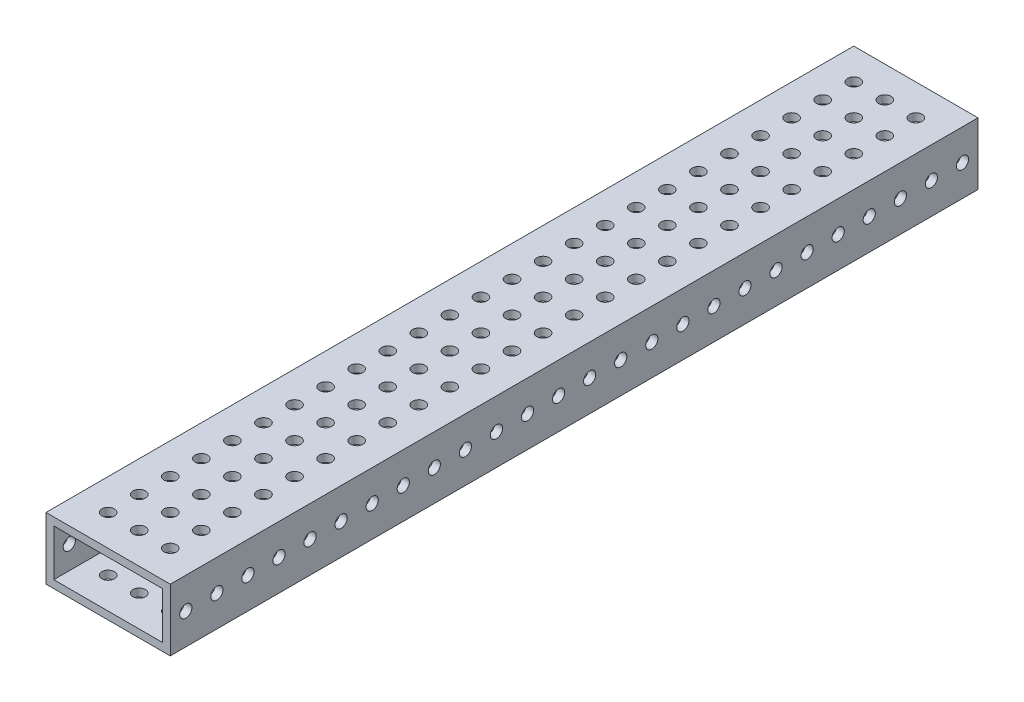
SolidWorks part; units mm, degrees
material "6061-T6 (SS)"
ref_plane "Front Plane" through (0, 0, 0) normal (0, 0, 1) x (1, 0, 0)
ref_plane "Top Plane" through (0, 0, 0) normal (0, 1, 0) x (1, 0, 0)
ref_plane "Right Plane" through (0, 0, 0) normal (1, 0, 0) x (0, 0, -1)
sketch "Sketch1" plane through (0, 0, 0) normal (0, 0, 1) x (1, 0, 0)
  line L0 (-22.225, 9.525) -> (22.225, 9.525)
  line L1 (-25.4, 12.7) -> (25.4, 12.7)
  line L2 (-25.4, 12.7) -> (-25.4, -12.7)
  line L3 (-25.4, -12.7) -> (25.4, -12.7)
  line L4 (25.4, 12.7) -> (25.4, -12.7)
  line L5 (22.225, 9.525) -> (22.225, -9.525)
  line L6 (-22.225, -9.525) -> (22.225, -9.525)
  line L7 (-22.225, 9.525) -> (-22.225, -9.525)
  line L8 (-25.4, 12.7) -> (25.4, -12.7) construction
  line L9 (25.4, 12.7) -> (-25.4, -12.7) construction
  point P5 (0, 0)
  dimension "D1" = 50.8
  dimension "D2" = 25.4
  dimension "D3" = 3.175
extrude "Boss-Extrude1" add sketch "Sketch1" along normal mid plane 330.2
sketch "Sketch2" plane through (0, 12.7, 0) normal (0, 1, 0) x (1, 0, 0)
  line L0 (25.4, -165.1) -> (-25.4, -165.1) construction
  line L1 (-25.4, -165.1) -> (-25.4, 165.1) construction
  line L2 (-12.7, -152.4) -> (0, -152.4) construction
  line L3 (0, -152.4) -> (12.7, -152.4) construction
  line L4 (25.4, 165.1) -> (-25.4, 165.1) construction
  circle A0 centre (0, -152.4) radius 2.5527
  circle A1 centre (12.7, -152.4) radius 2.5527
  circle A2 centre (-12.7, -152.4) radius 2.5527
  circle A3 centre (-12.7, -139.7) radius 2.5527
  circle A4 centre (0, -139.7) radius 2.5527
  circle A5 centre (12.7, -139.7) radius 2.5527
  circle A6 centre (-12.7, -127) radius 2.5527
  circle A7 centre (0, -127) radius 2.5527
  circle A8 centre (12.7, -127) radius 2.5527
  circle A9 centre (-12.7, -114.3) radius 2.5527
  circle A10 centre (0, -114.3) radius 2.5527
  circle A11 centre (12.7, -114.3) radius 2.5527
  circle A12 centre (-12.7, -101.6) radius 2.5527
  circle A13 centre (0, -101.6) radius 2.5527
  circle A14 centre (12.7, -101.6) radius 2.5527
  circle A15 centre (-12.7, -88.9) radius 2.5527
  circle A16 centre (0, -88.9) radius 2.5527
  circle A17 centre (12.7, -88.9) radius 2.5527
  circle A18 centre (-12.7, -76.2) radius 2.5527
  circle A19 centre (0, -76.2) radius 2.5527
  circle A20 centre (12.7, -76.2) radius 2.5527
  circle A21 centre (-12.7, -63.5) radius 2.5527
  circle A22 centre (0, -63.5) radius 2.5527
  circle A23 centre (12.7, -63.5) radius 2.5527
  circle A24 centre (-12.7, -50.8) radius 2.5527
  circle A25 centre (0, -50.8) radius 2.5527
  circle A26 centre (12.7, -50.8) radius 2.5527
  circle A27 centre (-12.7, -38.1) radius 2.5527
  circle A28 centre (0, -38.1) radius 2.5527
  circle A29 centre (12.7, -38.1) radius 2.5527
  circle A30 centre (-12.7, -25.4) radius 2.5527
  circle A31 centre (0, -25.4) radius 2.5527
  circle A32 centre (12.7, -25.4) radius 2.5527
  circle A33 centre (-12.7, -12.7) radius 2.5527
  circle A34 centre (0, -12.7) radius 2.5527
  circle A35 centre (12.7, -12.7) radius 2.5527
  circle A36 centre (-12.7, 0) radius 2.5527
  circle A37 centre (0, 0) radius 2.5527
  circle A38 centre (12.7, 0) radius 2.5527
  circle A39 centre (-12.7, 12.7) radius 2.5527
  circle A40 centre (0, 12.7) radius 2.5527
  circle A41 centre (12.7, 12.7) radius 2.5527
  circle A42 centre (-12.7, 25.4) radius 2.5527
  circle A43 centre (0, 25.4) radius 2.5527
  circle A44 centre (12.7, 25.4) radius 2.5527
  circle A45 centre (-12.7, 38.1) radius 2.5527
  circle A46 centre (0, 38.1) radius 2.5527
  circle A47 centre (12.7, 38.1) radius 2.5527
  circle A48 centre (-12.7, 50.8) radius 2.5527
  circle A49 centre (0, 50.8) radius 2.5527
  circle A50 centre (12.7, 50.8) radius 2.5527
  circle A51 centre (-12.7, 63.5) radius 2.5527
  circle A52 centre (0, 63.5) radius 2.5527
  circle A53 centre (12.7, 63.5) radius 2.5527
  circle A54 centre (-12.7, 76.2) radius 2.5527
  circle A55 centre (0, 76.2) radius 2.5527
  circle A56 centre (12.7, 76.2) radius 2.5527
  circle A57 centre (-12.7, 88.9) radius 2.5527
  circle A58 centre (0, 88.9) radius 2.5527
  circle A59 centre (12.7, 88.9) radius 2.5527
  circle A60 centre (-12.7, 101.6) radius 2.5527
  circle A61 centre (0, 101.6) radius 2.5527
  circle A62 centre (12.7, 101.6) radius 2.5527
  circle A63 centre (-12.7, 114.3) radius 2.5527
  circle A64 centre (0, 114.3) radius 2.5527
  circle A65 centre (12.7, 114.3) radius 2.5527
  circle A66 centre (-12.7, 127) radius 2.5527
  circle A67 centre (0, 127) radius 2.5527
  circle A68 centre (12.7, 127) radius 2.5527
  circle A69 centre (-12.7, 139.7) radius 2.5527
  circle A70 centre (0, 139.7) radius 2.5527
  circle A71 centre (12.7, 139.7) radius 2.5527
  circle A72 centre (-12.7, 152.4) radius 2.5527
  circle A73 centre (0, 152.4) radius 2.5527
  circle A74 centre (12.7, 152.4) radius 2.5527
  circle A75 centre (-12.7, 165.1) radius 2.5527 construction
  circle A76 centre (0, 165.1) radius 2.5527 construction
  circle A77 centre (12.7, 165.1) radius 2.5527 construction
  circle A78 centre (-12.7, 177.8) radius 2.5527
  circle A79 centre (0, 177.8) radius 2.5527
  circle A80 centre (12.7, 177.8) radius 2.5527
  circle A81 centre (-12.7, 190.5) radius 2.5527
  circle A82 centre (0, 190.5) radius 2.5527
  circle A83 centre (12.7, 190.5) radius 2.5527
  circle A84 centre (-12.7, 203.2) radius 2.5527
  circle A85 centre (0, 203.2) radius 2.5527
  circle A86 centre (12.7, 203.2) radius 2.5527
  circle A87 centre (-12.7, 215.9) radius 2.5527
  circle A88 centre (0, 215.9) radius 2.5527
  circle A89 centre (12.7, 215.9) radius 2.5527
  circle A90 centre (-12.7, 228.6) radius 2.5527
  circle A91 centre (0, 228.6) radius 2.5527
  circle A92 centre (12.7, 228.6) radius 2.5527
  circle A93 centre (-12.7, 241.3) radius 2.5527
  circle A94 centre (0, 241.3) radius 2.5527
  circle A95 centre (12.7, 241.3) radius 2.5527
  circle A96 centre (-12.7, 254) radius 2.5527
  circle A97 centre (0, 254) radius 2.5527
  circle A98 centre (12.7, 254) radius 2.5527
  circle A99 centre (-12.7, 266.7) radius 2.5527
  circle A100 centre (0, 266.7) radius 2.5527
  circle A101 centre (12.7, 266.7) radius 2.5527
  circle A108 centre (-12.7, 292.1) radius 2.5527 [skipped]
  circle A109 centre (0, 292.1) radius 2.5527 [skipped]
  circle A110 centre (12.7, 292.1) radius 2.5527 [skipped]
  circle A111 centre (-12.7, 279.4) radius 2.5527 [skipped]
  circle A112 centre (0, 279.4) radius 2.5527 [skipped]
  circle A113 centre (12.7, 279.4) radius 2.5527 [skipped]
  circle A114 centre (12.7, 279.4) radius 2.5527
  circle A115 centre (0, 279.4) radius 2.5527
  circle A116 centre (-12.7, 279.4) radius 2.5527
  circle A117 centre (12.7, 292.1) radius 2.5527
  circle A118 centre (0, 292.1) radius 2.5527
  circle A119 centre (-12.7, 292.1) radius 2.5527
  circle A120 centre (12.7, 304.8) radius 2.5527
  circle A121 centre (0, 304.8) radius 2.5527
  circle A122 centre (-12.7, 304.8) radius 2.5527
  circle A123 centre (12.7, 317.5) radius 2.5527
  circle A124 centre (0, 317.5) radius 2.5527
  circle A125 centre (-12.7, 317.5) radius 2.5527
  circle A126 centre (12.7, 330.2) radius 2.5527
  circle A127 centre (0, 330.2) radius 2.5527
  circle A128 centre (-12.7, 330.2) radius 2.5527
  circle A129 centre (12.7, 342.9) radius 2.5527
  circle A130 centre (0, 342.9) radius 2.5527
  circle A131 centre (-12.7, 342.9) radius 2.5527
  circle A132 centre (12.7, 355.6) radius 2.5527
  circle A133 centre (0, 355.6) radius 2.5527
  circle A134 centre (-12.7, 355.6) radius 2.5527
  circle A135 centre (12.7, 368.3) radius 2.5527
  circle A136 centre (0, 368.3) radius 2.5527
  circle A137 centre (-12.7, 368.3) radius 2.5527
  circle A138 centre (12.7, 381) radius 2.5527
  circle A139 centre (0, 381) radius 2.5527
  circle A140 centre (-12.7, 381) radius 2.5527
  circle A141 centre (12.7, 393.7) radius 2.5527
  circle A142 centre (0, 393.7) radius 2.5527
  circle A143 centre (-12.7, 393.7) radius 2.5527
  circle A144 centre (12.7, 406.4) radius 2.5527
  circle A145 centre (0, 406.4) radius 2.5527
  circle A146 centre (-12.7, 406.4) radius 2.5527
  circle A147 centre (12.7, 419.1) radius 2.5527
  circle A148 centre (0, 419.1) radius 2.5527
  circle A149 centre (-12.7, 419.1) radius 2.5527
  circle A150 centre (12.7, 431.8) radius 2.5527
  circle A151 centre (0, 431.8) radius 2.5527
  circle A152 centre (-12.7, 431.8) radius 2.5527
  point P210 (0, 0)
  point P211 (0, 0)
  dimension "D2" = 5.1054
  dimension "D4" = 12.7
  dimension "D1" = 12.7
  dimension "D3" = 25.4
  dimension "D6" = 12.7
  dimension "D7" = 101.6
  dimension "D5" = 36
  dimension "D8" = 14
extrude "Cut-Extrude1" cut sketch "Sketch2" against normal through all
sketch "Sketch4" plane through (25.4, 0, 0) normal (1, 0, 0) x (0, 0, -1)
  line L1 (-165.1, -12.7) -> (-165.1, 12.7) construction
  line L2 (-165.1, -12.7) -> (165.1, -12.7) construction
  circle A2 centre (-158.75, 0) radius 2.4892
  circle A3 centre (-146.05, 0) radius 2.4892
  circle A16 centre (-133.35, 0) radius 2.4892
  circle A17 centre (-120.65, 0) radius 2.4892
  circle A18 centre (-107.95, 0) radius 2.4892
  circle A19 centre (273.05, 0) radius 2.4892
  circle A20 centre (285.75, 0) radius 2.4892
  circle A21 centre (298.45, 0) radius 2.4892
  circle A22 centre (311.15, 0) radius 2.4892
  circle A23 centre (323.85, 0) radius 2.4892
  circle A24 centre (336.55, 0) radius 2.4892
  circle A25 centre (349.25, 0) radius 2.4892
  circle A26 centre (361.95, 0) radius 2.4892
  circle A27 centre (374.65, 0) radius 2.4892
  circle A28 centre (387.35, 0) radius 2.4892
  circle A29 centre (400.05, 0) radius 2.4892
  circle A30 centre (412.75, 0) radius 2.4892
  circle A31 centre (425.45, 0) radius 2.4892
  circle A32 centre (438.15, 0) radius 2.4892
  circle A35 centre (-95.25, 0) radius 2.4892
  circle A36 centre (-82.55, 0) radius 2.4892
  circle A37 centre (-69.85, 0) radius 2.4892
  circle A38 centre (-57.15, 0) radius 2.4892
  circle A39 centre (-44.45, 0) radius 2.4892
  circle A40 centre (-31.75, 0) radius 2.4892
  circle A41 centre (-19.05, 0) radius 2.4892
  circle A42 centre (-6.35, 0) radius 2.4892
  circle A43 centre (6.35, 0) radius 2.4892
  circle A44 centre (19.05, 0) radius 2.4892
  circle A45 centre (31.75, 0) radius 2.4892
  circle A46 centre (44.45, 0) radius 2.4892
  circle A47 centre (57.15, 0) radius 2.4892
  circle A48 centre (69.85, 0) radius 2.4892
  circle A49 centre (82.55, 0) radius 2.4892
  circle A50 centre (95.25, 0) radius 2.4892
  circle A51 centre (107.95, 0) radius 2.4892
  circle A52 centre (120.65, 0) radius 2.4892
  circle A53 centre (133.35, 0) radius 2.4892
  circle A54 centre (146.05, 0) radius 2.4892
  circle A55 centre (158.75, 0) radius 2.4892
  circle A56 centre (171.45, 0) radius 2.4892
  circle A57 centre (184.15, 0) radius 2.4892
  circle A58 centre (196.85, 0) radius 2.4892
  circle A59 centre (209.55, 0) radius 2.4892
  circle A60 centre (222.25, 0) radius 2.4892
  circle A61 centre (234.95, 0) radius 2.4892
  circle A62 centre (247.65, 0) radius 2.4892
  circle A63 centre (260.35, 0) radius 2.4892
  dimension "D2" = 4.9784
  dimension "D1" = 6.35
  dimension "D3" = 12.7
  dimension "D4" = 12.7
  dimension "D5" = 34
  dimension "D6" = 10
  dimension "D7" = 6
extrude "Cut-Extrude3" cut sketch "Sketch4" against normal through all
